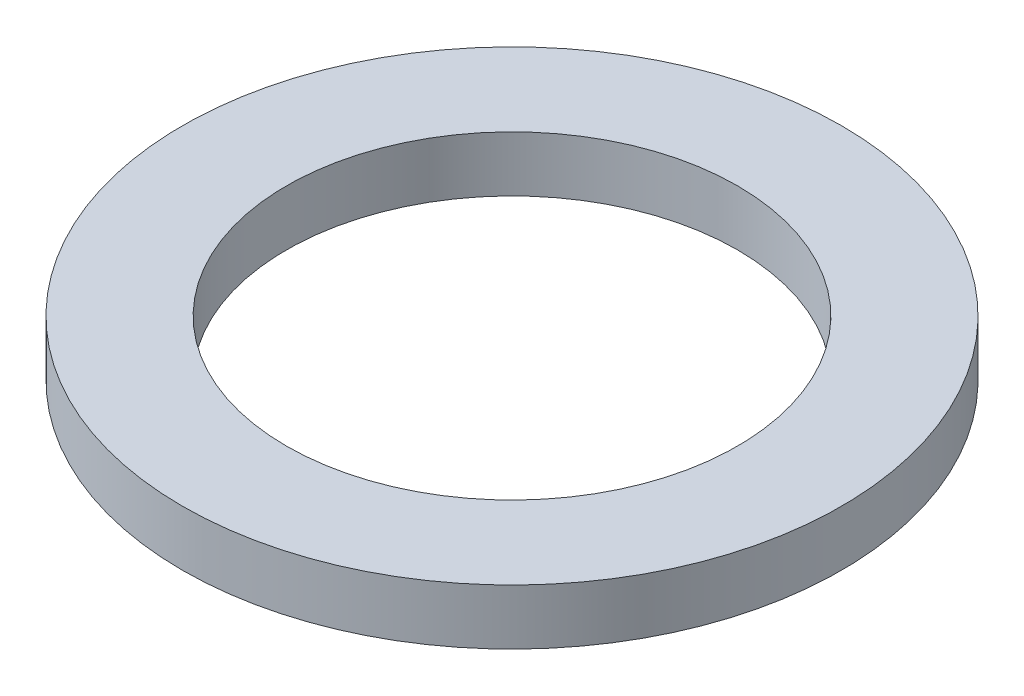
SolidWorks part; units mm, degrees
ref_plane "Front Plane" through (0, 0, 0) normal (0, 0, 1) x (1, 0, 0)
ref_plane "Top Plane" through (0, 0, 0) normal (0, 1, 0) x (1, 0, 0)
ref_plane "Right Plane" through (0, 0, 0) normal (1, 0, 0) x (0, 0, -1)
sketch "Sketch1" plane through (0, 0, 0) normal (0, 1, 0) x (1, 0, 0)
  circle A0 centre (0, 0) radius 47.5
  dimension "FLANGE_OD" = 95
extrude "Boss-Extrude1" add sketch "Sketch1" along normal blind 8
sketch "Sketch2" plane through (0, 0, 0) normal (0, 1, 0) x (1, 0, 0)
  circle A0 centre (0, 0) radius 32.5
  dimension "BORE_D" = 65
extrude "Cut-Extrude1" cut sketch "Sketch2" along normal through all
sketch "Sketch3" plane through (0, 8, 0) normal (0, 1, 0) x (1, 0, 0)
  circle A0 centre (0, 0) radius 17.7406 construction
  circle A1 centre (-17.7406, 0) radius 1.7176
  dimension "BOLT_D" = 3.4352
  dimension "BOLT_PCD" = 35.4813
extrude "Cut-Extrude2" cut sketch "Sketch3" against normal blind 6.0442 rebuild error yes
pattern_circular "CirPattern1" count 5 over 360 rebuild error yes
